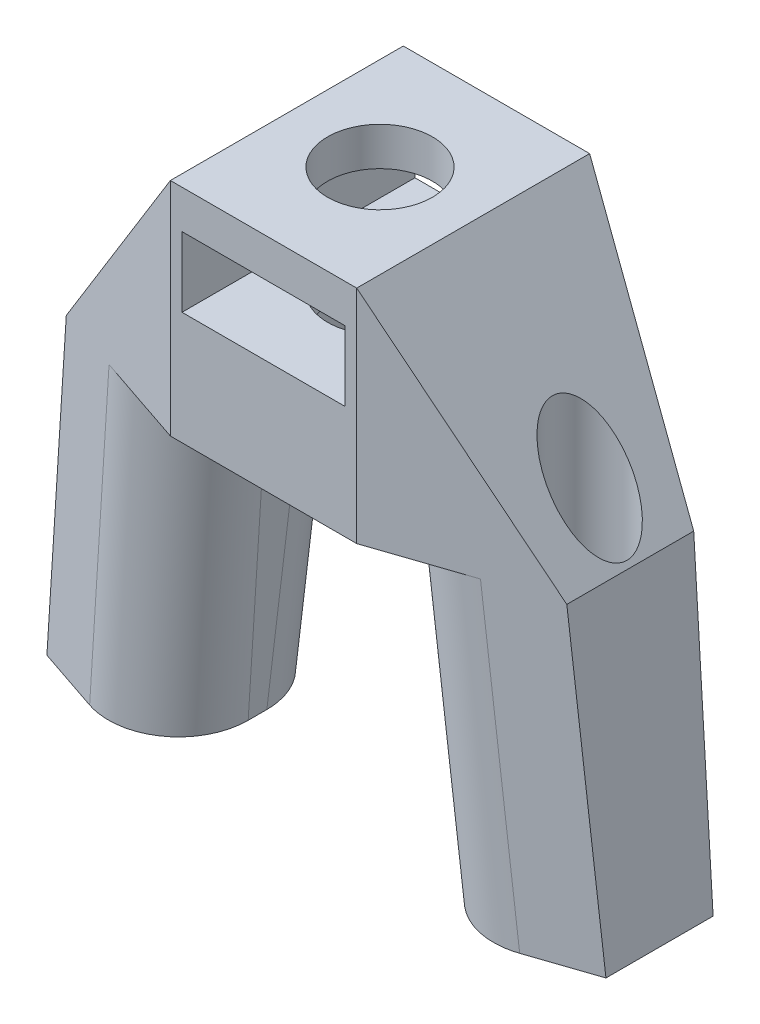
SolidWorks part; units mm, degrees
material "ABS"
ref_plane "Plan de face" through (0, 0, 0) normal (0, 0, 1) x (1, 0, 0)
ref_plane "Plan de dessus" through (0, 0, 0) normal (0, 1, 0) x (1, 0, 0)
ref_plane "Plan de droite" through (0, 0, 0) normal (1, 0, 0) x (0, 0, -1)
sketch "Esquisse1" plane through (0, 0, 0) normal (0, 0, 1) x (1, 0, 0)
  line L0 (0, 10.4639) -> (0, -9.5361) construction
  line L2 (-4, -12.7861) -> (4, -12.7861) construction
  line L3 (-4, -12.7861) -> (-4, -6.2861) construction
  line L4 (-4, -6.2861) -> (4, -6.2861) construction
  line L5 (4, -12.7861) -> (4, -6.2861) construction
  line L6 (-4, -12.7861) -> (4, -6.2861) construction
  line L7 (-4, -6.2861) -> (4, -12.7861) construction
  line L8 (-4, 7.2139) -> (4, 7.2139)
  line L9 (-4, 7.2139) -> (-4, 13.7139)
  line L10 (-4, 13.7139) -> (4, 13.7139)
  line L11 (4, 7.2139) -> (4, 13.7139)
  line L12 (-4, 7.2139) -> (4, 13.7139) construction
  line L13 (-4, 13.7139) -> (4, 7.2139) construction
  dimension "D1" = 20
  dimension "D2" = 6.5
  dimension "D3" = 4
extrude "Joint body" add sketch "Esquisse1" along normal blind 5 and the other way blind 5
sketch "Esquisse2" plane through (0, 7.2139, 0) normal (0, -1, 0) x (1, 0, 0)
  line L0 (-4, 0) -> (4, 0) construction
  circle A0 centre (0, 0) radius 3.7
  dimension "D1" = 7.4
extrude "BearingHole" cut sketch "Esquisse2" against normal blind 3.2
sketch "Esquisse4" plane through (0, 13.7139, 0) normal (0, 1, 0) x (1, 0, 0)
  line L1 (-4, -5) -> (4, -5)
  line L2 (-4, -5) -> (-4, 5)
  line L3 (-4, 5) -> (4, 5)
  line L4 (4, -5) -> (4, 5)
  line L5 (-4, -5) -> (4, 5) construction
  line L6 (-4, 5) -> (4, -5) construction
extrude "LockerExtrude" add sketch "Esquisse4" along normal blind 3
sketch "Esquisse5" plane through (0, 16.7139, 0) normal (0, 1, 0) x (1, 0, 0)
  circle A0 centre (0, 0) radius 2.25
  dimension "D1" = 4.5
extrude "AxeHole" cut sketch "Esquisse5" against normal blind 16
sketch "Esquisse6" plane through (0, 0, 5) normal (0, 0, 1) x (1, 0, 0)
  line L0 (0, 16.7139) -> (0, 10.4139) construction
  line L1 (-4, 16.7139) -> (4, 16.7139) construction
  line L3 (0, 10.4639) -> (0, -9.5361) construction
  line L4 (-3.5, 12.0639) -> (3.5, 12.0639)
  line L5 (-3.5, 12.0639) -> (-3.5, 15.0639)
  line L6 (-3.5, 15.0639) -> (3.5, 15.0639)
  line L7 (3.5, 12.0639) -> (3.5, 15.0639)
  line L8 (-3.5, 12.0639) -> (3.5, 15.0639) construction
  line L9 (-3.5, 15.0639) -> (3.5, 12.0639) construction
  line L10 (-2.25, 10.4139) -> (2.25, 10.4139) construction
  point P6 (0, 13.5639)
  dimension "D1" = 3
  dimension "D2" = 7
extrude "LockerHole" cut sketch "Esquisse6" against normal blind 16
sketch "Esquisse7" plane through (0, 0, 0) normal (0, 0, 1) x (1, 0, 0)
  line L0 (12, -6.2861) -> (10.7436, 7.188)
  line L1 (4, -6.2861) -> (12, -6.2861) construction
  line L2 (9, -6.2861) -> (9, 1.0696) construction
  line L3 (10.7436, 7.188) -> (4, 16.7139)
  line L4 (4, 16.7139) -> (4, 7.2139)
  line L6 (4, 7.2139) -> (5.2588, -6.2861)
  line L7 (5.2588, -6.2861) -> (12, -6.2861)
  dimension "D1" = 8
  dimension "D2" = 3
extrude "FixationExtrude" add sketch "Esquisse7" along normal up to surface (5 mm away) and the other way up to surface (5 mm away) up to face at (0, 13.5639, 5) other way up to face at (0, 13.5639, -5)
sketch "Esquisse8" plane through (0, -6.2861, 0) normal (0, -1, 0) x (1, 0, 0)
  line L0 (12, 0) -> (9, 0) construction
  line L1 (12, 5) -> (12, -5) construction
  circle A0 centre (9, 0) radius 1.6
  dimension "D1" = 3.2
  dimension "D2" = 3
extrude "FixationHole" cut sketch "Esquisse8" against normal blind 19.5
sketch "Esquisse10" plane through (0, -6.2861, 0) normal (0, -1, 0) x (1, 0, 0)
  line L1 (12, 5) -> (12, -5) construction
  line L3 (12, 2.3) -> (12, 5)
  line L5 (12, -2.3) -> (12, -5)
  line L7 (12, -2.3) -> (12, 0) construction
  line L8 (12, 0) -> (12, 2.3) construction
  line L9 (4, -5) -> (4, 5) construction
  line L10 (12, 2.3) -> (4, 5)
  line L11 (4, 5) -> (12, 5)
  line L12 (12, -5) -> (4, -5)
  line L13 (4, -5) -> (12, -2.3)
  dimension "D1" = 4.6
extrude "FixationProfile" cut sketch "Esquisse10" against normal through all
mirror "Symétrie3" about plane through (0, 0, 0) normal (1, 0, 0) of "FixationProfile", "FixationHole", "FixationExtrude"
fillet "Congé1" radius 3 4 edges at (-4.6294, 0.4639, -4.7876) (-4.6294, 0.4639, 4.7876) (4.6294, 0.4639, -4.7876) (4.6294, 0.4639, 4.7876)
equation "\"entretoiseBearing\"= 1.5mm"
equation "\"length_tibia\"= 206mm"
equation "\"length_femur\"= 117mm"
equation "\"length_coxa\"= 27mm"
equation "\"height\"= 40mm"
equation "\"width\"= 100mm"
equation "\"lever\"= 40mm"
equation "\"errorFlat\"= 0.20mm"
equation "\"errorCircle\"= 0.40mm"
equation "\"cuticule\"=1.5mm"
equation "\"cuticule_attach_w\"=10mm"
equation "\"cuticule_attach_h\"=2.5mm"
equation "\"depthMagnet\"= 1mm"
equation "\"insert_d\" = 3.2mm"
equation "\"insert_l\" = 5mm"
equation "\"D1@Esquisse8\"=\"insert_d\""
equation "\"D1@Esquisse5\"=\"entretoiseBearing\"+3"
equation "\"D1@Esquisse2\"=\"errorCircle\"+7"
equation "\"D1@BearingHole\"=\"errorFlat\"+3"
equation "\"D1@Esquisse10\"=5-2*\"errorFlat\""
